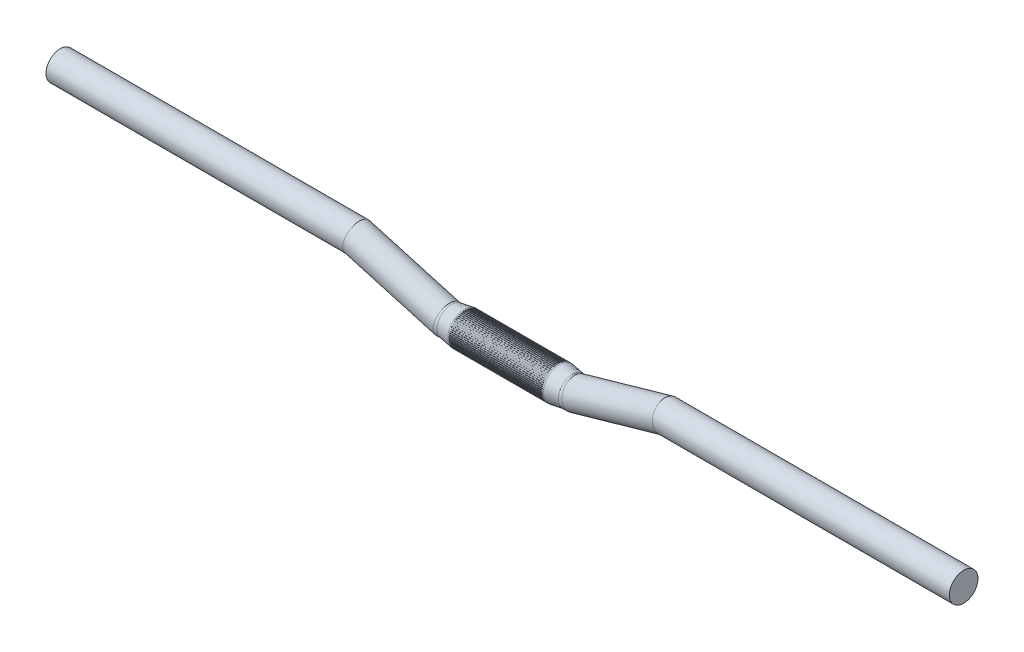
SolidWorks part; units mm, degrees
material "Alliage 2024"
ref_plane "Plan de face" through (0, 0, 0) normal (0, 0, 1) x (1, 0, 0)
ref_plane "Plan de dessus" through (0, 0, 0) normal (0, 1, 0) x (1, 0, 0)
ref_plane "Plan de droite" through (0, 0, 0) normal (1, 0, 0) x (0, 0, -1)
sketch "Esquisse1" plane through (0, 0, 0) normal (0, 0, 1) x (1, 0, 0)
  line L0 (-50, 0) -> (50, 0)
  line L1 (120, 20) -> (350, 20)
  line L2 (-120, 20) -> (-350, 20)
  spline S0 degree 1 poles (50, 0) (120, 20) knots 0 0 1 1
  spline S1 degree 1 poles (-50, 0) (-120, 20) knots 0 0 1 1
  dimension "D1" = 100
  dimension "D2" = 50
  dimension "D3" = 70
  dimension "D4" = 70
  dimension "D5" = 230
  dimension "D6" = 230
  dimension "D7" = 20
sketch "Esquisse2" plane through (0, 0, 0) normal (1, 0, 0) x (0, 0, -1)
  circle A0 centre (0, 0) radius 11.1
  dimension "D1" = 22.2
sweep "Balayage1" add profiles "Esquisse2" path "Esquisse1"
sketch "Esquisse4" plane through (0, 0, 0) normal (-1, 0, 0) x (0, 0, 1)
  circle A0 centre (0, 0) radius 12.7
  dimension "D1" = 25.4
extrude "Boss.-Extru.1" add sketch "Esquisse4" against normal blind 47
sketch "Esquisse5" plane through (0, 0, 0) normal (-1, 0, 0) x (0, 0, 1)
  line L1 (12.95, 0.25) -> (12.45, 0.25)
  line L2 (12.95, 0.25) -> (12.95, -0.25)
  line L3 (12.95, -0.25) -> (12.45, -0.25)
  line L4 (12.45, 0.25) -> (12.45, -0.25)
  line L5 (12.95, 0.25) -> (12.45, -0.25) construction
  line L6 (12.95, -0.25) -> (12.45, 0.25) construction
  circle A0 centre (0, 0) radius 12.7 construction
  point P0 (12.7, 0)
  dimension "D1" = 0.5
  dimension "D2" = 0.5
extrude "Enlèv. mat.-Extru.1" cut sketch "Esquisse5" against normal blind 36
pattern_circular "Répétition circulaire1" count 68 over 360 about axis through (0, 0, 0) along (-1, 0, 0) of "Enlèv. mat.-Extru.1"
mirror "Symétrie1" of "Répétition circulaire1", "Enlèv. mat.-Extru.1", "Boss.-Extru.1", "Balayage1"
chamfer "Chanfrein3" distance 10 angle 9 2 edges at (47, 0, 12.7) (-47, 0, 12.7) first distance on face at (47, 0, 12.7)
ref_point "Point1"
ref_axis "Axe1" through (-363.2564, 20, 0) along (1, 0, 0)
